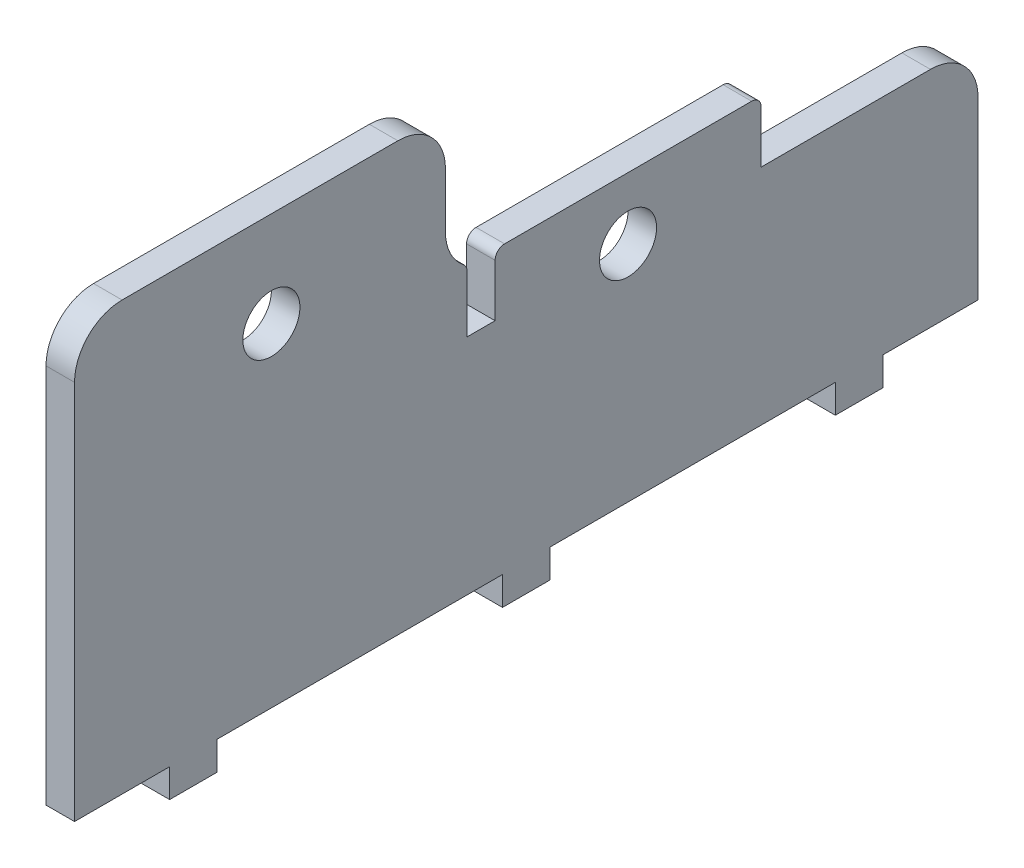
SolidWorks part; units mm, degrees
ref_plane "Front Plane" through (0, 0, 0) normal (0, 0, 1) x (1, 0, 0)
ref_plane "Top Plane" through (0, 0, 0) normal (0, 1, 0) x (1, 0, 0)
ref_plane "Right Plane" through (0, 0, 0) normal (1, 0, 0) x (0, 0, -1)
sketch "Sketch1" plane through (0, 0, 0) normal (1, 0, 0) x (0, 0, -1)
  line L1 (65, 0) -> (-30, 0)
  line L2 (65, 0) -> (65, 30)
  line L3 (65, 30) -> (-30, 30)
  line L4 (-30, 0) -> (-30, 30)
  line L5 (55, 0) -> (-55, 0) construction
  point P0 (0, 0)
  dimension "D2" = 30
  dimension "D1" = 95
  dimension "D4" = 30
extrude "Boss-Extrude1" add sketch "Sketch1" along normal blind 3
sketch "Sketch4" plane through (0, 0, 0) normal (0, 1, 0) x (1, 0, 0)
  line L0 (3, -30) -> (3, 65) construction
  line L1 (3, -20) -> (0, -20)
  line L2 (3, -20) -> (3, -15)
  line L3 (3, -15) -> (0, -15)
  line L4 (0, -20) -> (0, -15)
  line L5 (0, -30) -> (0, 65) construction
  line L6 (3, -30) -> (0, -30) construction
  dimension "D1" = 10
  dimension "D2" = 5
extrude "Boss-Extrude2" add sketch "Sketch4" against normal blind 3
sketch "Sketch5" plane through (0, 30, 0) normal (0, 1, 0) x (1, 0, 0)
  line L0 (0, 65) -> (0, -30) construction
  line L1 (0, 9) -> (3, 9)
  line L2 (0, 9) -> (0, -30)
  line L3 (0, -30) -> (3, -30)
  line L4 (3, 9) -> (3, -30)
  line L5 (3, 65) -> (3, -30) construction
  line L6 (3, -30) -> (0, -30) construction
  dimension "D1" = 39
extrude "Boss-Extrude3" add sketch "Sketch5" along normal blind 15
sketch "Sketch2" plane through (3, 0, 0) normal (1, 0, 0) x (0, 0, -1)
  line L7 (-26.9862, 0) -> (-28.4862, -10) construction
  line L16 (1.65, 0) -> (-1.65, 0) construction
  line L17 (65, 0) -> (65, 30) construction
  circle A1 centre (28.2, 23.5) radius 3
  circle A8 centre (-9.3, 35) radius 3
  point P6 (-28.4862, -10)
  point P11 (28.0724, -10)
  dimension "D1" = 6
  dimension "D3" = 74.3
  dimension "D4" = 6
  dimension "D2" = 35
  dimension "D5" = 36.8
extrude "Cut-Extrude1" cut sketch "Sketch2" against normal through all
pattern_linear "LPattern1" count 3 spacing 35 along (0, 0, -1) of "Boss-Extrude2"
sketch "Sketch6" plane through (3, 0, 0) normal (1, 0, 0) x (0, 0, -1)
  line L0 (65, 30) -> (9, 30) construction
  line L1 (11.2714, 32.2062) -> (14.2214, 32.2062)
  line L2 (11.2714, 32.2062) -> (11.2714, 23.5)
  line L3 (11.2714, 23.5) -> (14.2214, 23.5)
  line L4 (14.2214, 32.2062) -> (14.2214, 23.5)
  line L5 (-15, 0) -> (15, 0) construction
  line L6 (42.2, 30) -> (65, 30)
  line L7 (42.2, 30) -> (42.2, 23.5)
  line L8 (42.2, 23.5) -> (65, 23.5)
  line L9 (65, 30) -> (65, 23.5)
  line L10 (65, 0) -> (65, 30) construction
  dimension "D1" = 23.5
  dimension "D2" = 2.95
  dimension "D3" = 14
extrude "Cut-Extrude2" cut sketch "Sketch6" against normal through all
fillet "Fillet3" radius 5 4 edges at (1.5, 45, 30) (1.5, 45, -9) (1.5, 30, -9) (1.5, 23.5, -65)
fillet "Fillet4" radius 1 3 edges at (1.5, 30, -11.2714) (1.5, 30, -14.2214) (1.5, 30, -42.2)
